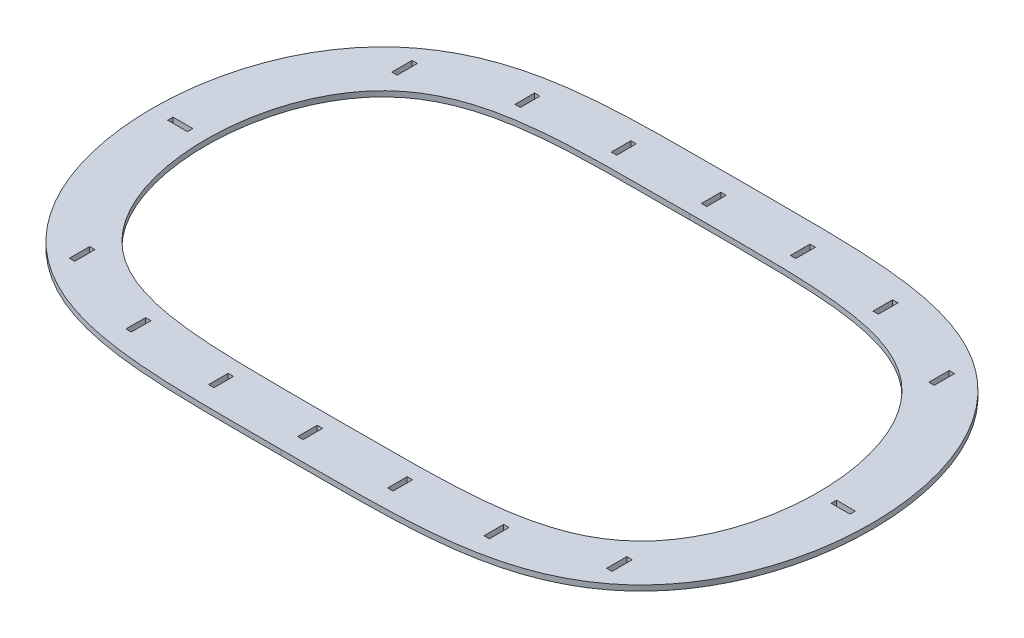
SolidWorks part; units mm, degrees
ref_plane "Front Plane" through (0, 0, 0) normal (0, 0, 1) x (1, 0, 0)
ref_plane "Top Plane" through (0, 0, 0) normal (0, 1, 0) x (1, 0, 0)
ref_plane "Right Plane" through (0, 0, 0) normal (1, 0, 0) x (0, 0, -1)
sketch "Sketch1" plane through (0, 0, 0) normal (0, 1, 0) x (1, 0, 0)
  spline S0 degree 4 poles (0, 129.0994) (4.3298, 129.0999) (12.9895, 129.0995) (25.9763, 129.0992) (43.2902, 129.014) (60.6007, 128.6712) (77.8947, 127.8129) (95.543, 126.046) (113.014, 122.896) (130.0464, 117.7971) (146.1581, 110.2269) (160.4313, 100.265) (172.6933, 87.9119) (182.6634, 73.6634) (190.3404, 58.0791) (195.8654, 41.6227) (199.4008, 24.6362) (201.0699, 7.3707) (200.9352, -9.9735) (198.9912, -27.2107) (195.1663, -44.1354) (189.3287, -60.4854) (181.3147, -75.9018) (170.9944, -89.9023) (157.8662, -102.4377) (141.9679, -112.6829) (124.642, -119.7567) (106.7084, -124.2192) (88.4462, -126.9034) (70.0513, -128.3227) (45.6298, -129.0998) (25.3491, -129.0993) (10.1399, -129.0994) (0, -129.0994) knots 0 0 0 0 0 0.03122 0.06244 0.093642 0.124843 0.156053 0.187263 0.221451 0.252662 0.283872 0.315082 0.346292 0.377502 0.408713 0.439923 0.471133 0.502344 0.533554 0.564765 0.595975 0.627185 0.658396 0.689606 0.720816 0.757371 0.793926 0.823852 0.853778 0.890332 0.926886 1 1 1 1 1 construction
  spline S1 degree 4 poles (0, 129.0994) (4.3298, 129.0999) (12.9895, 129.0995) (25.9763, 129.0992) (43.2902, 129.014) (60.6007, 128.6712) (77.8947, 127.8129) (95.543, 126.046) (113.014, 122.896) (130.0464, 117.7971) (146.1581, 110.2269) (160.4313, 100.265) (172.6933, 87.9119) (182.6634, 73.6634) (190.3404, 58.0791) (195.8654, 41.6227) (199.4008, 24.6362) (201.0699, 7.3707) (200.9352, -9.9735) (198.9912, -27.2107) (195.1663, -44.1354) (189.3287, -60.4854) (181.3147, -75.9018) (170.9944, -89.9023) (157.8662, -102.4377) (141.9679, -112.6829) (124.642, -119.7567) (106.7084, -124.2192) (88.4462, -126.9034) (70.0513, -128.3227) (45.6298, -129.0998) (25.3491, -129.0993) (10.1399, -129.0994) (0, -129.0994) knots 0 0 0 0 0 0.03122 0.06244 0.093642 0.124843 0.156053 0.187263 0.221451 0.252662 0.283872 0.315082 0.346292 0.377502 0.408713 0.439923 0.471133 0.502344 0.533554 0.564765 0.595975 0.627185 0.658396 0.689606 0.720816 0.757371 0.793926 0.823852 0.853778 0.890332 0.926886 1 1 1 1 1
  spline S2 degree 4 poles (0, 129.0994) (-4.3298, 129.0999) (-12.9895, 129.0995) (-25.9763, 129.0992) (-43.2902, 129.014) (-60.6007, 128.6712) (-77.8947, 127.8129) (-95.543, 126.046) (-113.014, 122.896) (-130.0464, 117.7971) (-146.1581, 110.2269) (-160.4313, 100.265) (-172.6933, 87.9119) (-182.6634, 73.6634) (-190.3404, 58.0791) (-195.8654, 41.6227) (-199.4008, 24.6362) (-201.07, 7.3707) (-200.9352, -9.9735) (-198.9912, -27.2107) (-195.1663, -44.1354) (-189.3287, -60.4854) (-181.3147, -75.9018) (-170.9944, -89.9023) (-157.8662, -102.4377) (-141.9679, -112.6829) (-124.642, -119.7567) (-106.7084, -124.2192) (-88.4462, -126.9034) (-70.0513, -128.3227) (-45.6298, -129.0998) (-25.3491, -129.0993) (-10.1399, -129.0994) (0, -129.0994) knots 0 0 0 0 0 0.03122 0.06244 0.093642 0.124843 0.156053 0.187263 0.221451 0.252662 0.283872 0.315082 0.346292 0.377502 0.408713 0.439923 0.471133 0.502344 0.533554 0.564765 0.595975 0.627185 0.658396 0.689606 0.720816 0.757371 0.793926 0.823852 0.853778 0.890332 0.926886 1 1 1 1 1 construction
  spline S3 degree 4 poles (0, 129.0994) (-4.3298, 129.0999) (-12.9895, 129.0995) (-25.9763, 129.0992) (-43.2902, 129.014) (-60.6007, 128.6712) (-77.8947, 127.8129) (-95.543, 126.046) (-113.014, 122.896) (-130.0464, 117.7971) (-146.1581, 110.2269) (-160.4313, 100.265) (-172.6933, 87.9119) (-182.6634, 73.6634) (-190.3404, 58.0791) (-195.8654, 41.6227) (-199.4008, 24.6362) (-201.07, 7.3707) (-200.9352, -9.9735) (-198.9912, -27.2107) (-195.1663, -44.1354) (-189.3287, -60.4854) (-181.3147, -75.9018) (-170.9944, -89.9023) (-157.8662, -102.4377) (-141.9679, -112.6829) (-124.642, -119.7567) (-106.7084, -124.2192) (-88.4462, -126.9034) (-70.0513, -128.3227) (-45.6298, -129.0998) (-25.3491, -129.0993) (-10.1399, -129.0994) (0, -129.0994) knots 0 0 0 0 0 0.03122 0.06244 0.093642 0.124843 0.156053 0.187263 0.221451 0.252662 0.283872 0.315082 0.346292 0.377502 0.408713 0.439923 0.471133 0.502344 0.533554 0.564765 0.595975 0.627185 0.658396 0.689606 0.720816 0.757371 0.793926 0.823852 0.853778 0.890332 0.926886 1 1 1 1 1
extrude "body" add sketch "Sketch1" along normal blind 3 contours S1 S3
sketch "Sketch6" plane through (0, 3, 0) normal (0, 1, 0) x (1, 0, 0)
  spline S5 degree 3 poles (-1285.0609, -2635.3961) (-864.743, -75.7384) (-425.088, -99.3062) (19.1852, -99.0955) (23.9815, -99.0904) (33.5738, -99.0537) (38.3699, -99.0221) (47.9616, -98.8962) (52.7579, -98.802) (62.3467, -98.4962) (67.1336, -98.285) (76.6828, -97.6696) (81.4451, -97.2657) (90.9316, -96.1585) (95.6558, -95.456) (102.6989, -94.0635) (105.0393, -93.5425) (108.5366, -92.6558) (109.7001, -92.3427) (112.0221, -91.6775) (113.1817, -91.3249) (118.9246, -89.468) (123.3747, -87.6745) (129.7643, -84.3748) (131.8465, -83.1733) (134.8899, -81.2003) (135.894, -80.5119) (137.8536, -79.0903) (138.8101, -78.3567) (143.4771, -74.5763) (146.8407, -71.1906) (150.6186, -66.542) (151.3528, -65.5915) (152.7797, -63.6497) (153.4733, -62.657) (155.4863, -59.6292) (156.7253, -57.5647) (160.1696, -51.2497) (162.1054, -46.8788) (164.5604, -40.1222) (165.3033, -37.8364) (166.3108, -34.36) (166.6291, -33.1922) (167.2268, -30.8567) (167.507, -29.6871) (168.8178, -23.8304) (169.5816, -19.117) (170.5999, -9.6403) (170.8539, -4.8769) (170.8586, 2.3051) (170.7971, 4.7053) (170.6075, 8.3151) (170.528, 9.5208) (170.3371, 11.9209) (170.2256, 13.117) (169.5883, 19.0778) (168.8243, 23.784) (166.7551, 33.0633) (165.4507, 37.6366) (163.0193, 44.3799) (162.1291, 46.6081) (160.6593, 49.9173) (160.1456, 51.0173) (159.078, 53.1894) (158.524, 54.2618) (155.6502, 59.5536) (153.0206, 63.5638) (149.2401, 68.2433) (148.4591, 69.1624) (146.8451, 70.9655) (146.0094, 71.852) (143.4475, 74.429) (141.6634, 76.0417) (136.0871, 80.5693) (132.0698, 83.1727) (126.7078, 85.9558) (125.6156, 86.4903) (123.4176, 87.5057) (122.3112, 87.9872) (118.9711, 89.3599) (116.7168, 90.1793) (109.885, 92.3962) (105.2389, 93.5553) (98.1742, 94.9611) (95.8032, 95.3737) (91.0346, 96.1061) (88.6465, 96.4244) (81.481, 97.263) (76.6986, 97.6685) (67.1268, 98.2855) (62.3375, 98.4965) (52.7547, 98.802) (47.9612, 98.8963) (38.372, 99.0221) (33.5762, 99.0536) (23.9839, 99.0903) (19.1872, 99.0954) (-464.0952, 99.336) (-943.5394, 72.5987) (-1333.0254, 2577.4402) knots -2.832138 -2.832138 -2.832138 -2.832138 0.03125 0.03125 0.0625 0.0625 0.09375 0.09375 0.125 0.125 0.15625 0.15625 0.1875 0.1875 0.21875 0.21875 0.234375 0.234375 0.242188 0.242188 0.25 0.25 0.28125 0.28125 0.296875 0.296875 0.304688 0.304688 0.3125 0.3125 0.34375 0.34375 0.351563 0.351563 0.359375 0.359375 0.375 0.375 0.40625 0.40625 0.421875 0.421875 0.429688 0.429688 0.4375 0.4375 0.46875 0.46875 0.5 0.5 0.515625 0.515625 0.523438 0.523438 0.53125 0.53125 0.5625 0.5625 0.59375 0.59375 0.609375 0.609375 0.617188 0.617188 0.625 0.625 0.65625 0.65625 0.664063 0.664063 0.671875 0.671875 0.6875 0.6875 0.71875 0.71875 0.726563 0.726563 0.734375 0.734375 0.75 0.75 0.78125 0.78125 0.796875 0.796875 0.8125 0.8125 0.84375 0.84375 0.875 0.875 0.90625 0.90625 0.9375 0.9375 0.96875 0.96875 4.085999 4.085999 4.085999 4.085999 only from (0, -99.0994) to (0, 99.0994)
  spline S6 degree 3 poles (1397.3598, 2549.0539) (939.196, 72.8031) (462.3033, 99.3351) (-19.1856, 99.0954) (-23.9819, 99.0903) (-33.5745, 99.0536) (-38.3706, 99.0221) (-47.9625, 98.8962) (-52.7589, 98.802) (-62.3478, 98.4961) (-67.1348, 98.285) (-76.6842, 97.6695) (-81.4467, 97.2655) (-90.9333, 96.1583) (-95.6577, 95.4559) (-102.701, 94.0631) (-105.0415, 93.5419) (-108.5389, 92.655) (-109.7024, 92.3419) (-112.0245, 91.6767) (-113.184, 91.3242) (-118.9268, 89.4676) (-123.3764, 87.6734) (-129.7661, 84.374) (-131.8484, 83.1724) (-134.8917, 81.1991) (-135.8958, 80.5106) (-137.8552, 79.089) (-138.8116, 78.3554) (-143.4783, 74.5751) (-146.8418, 71.1894) (-150.6197, 66.5406) (-151.354, 65.59) (-152.7809, 63.6482) (-153.4746, 62.6552) (-155.4873, 59.6275) (-156.7262, 57.5631) (-160.1704, 51.2481) (-162.1061, 46.8771) (-164.561, 40.1203) (-165.3039, 37.8343) (-166.3115, 34.3577) (-166.6296, 33.19) (-167.2273, 30.8546) (-167.5074, 29.685) (-168.8181, 23.8284) (-169.5818, 19.1151) (-170.6, 9.6383) (-170.854, 4.8748) (-170.8586, -2.3075) (-170.797, -4.7078) (-170.6074, -8.3179) (-170.5278, -9.5236) (-170.3369, -11.9235) (-170.2254, -13.1195) (-169.588, -19.0801) (-168.8239, -23.7862) (-166.7545, -33.0656) (-165.4499, -37.6391) (-163.0181, -44.3828) (-162.1279, -46.6111) (-160.6577, -49.9206) (-160.1439, -51.0207) (-159.0763, -53.1926) (-158.5224, -54.2649) (-155.6487, -59.5563) (-153.0188, -63.5663) (-149.2378, -68.246) (-148.4568, -69.1651) (-146.8426, -70.9683) (-146.0067, -71.8547) (-143.4449, -74.4313) (-141.661, -76.0438) (-136.0848, -80.5711) (-132.067, -83.1741) (-126.7046, -85.9575) (-125.6124, -86.4921) (-123.4146, -87.5073) (-122.3081, -87.9887) (-118.9681, -89.3609) (-116.7139, -90.18) (-109.8822, -92.3972) (-105.2359, -93.5559) (-98.1709, -94.9615) (-95.7998, -95.3742) (-91.0309, -96.1066) (-88.6431, -96.4249) (-81.478, -97.2633) (-76.6958, -97.6687) (-67.1244, -98.2856) (-62.3352, -98.4966) (-52.7528, -98.8021) (-47.9595, -98.8963) (-38.3706, -99.0221) (-33.5751, -99.0537) (-23.983, -99.0904) (-19.1865, -99.0955) (426.659, -99.307) (868.5614, -75.5661) (1217.4028, -2663.1697) knots -3.074556 -3.074556 -3.074556 -3.074556 0.03125 0.03125 0.0625 0.0625 0.09375 0.09375 0.125 0.125 0.15625 0.15625 0.1875 0.1875 0.21875 0.21875 0.234375 0.234375 0.242187 0.242187 0.25 0.25 0.28125 0.28125 0.296875 0.296875 0.304687 0.304687 0.3125 0.3125 0.34375 0.34375 0.351562 0.351562 0.359375 0.359375 0.375 0.375 0.40625 0.40625 0.421875 0.421875 0.429687 0.429687 0.4375 0.4375 0.46875 0.46875 0.5 0.5 0.515625 0.515625 0.523437 0.523437 0.53125 0.53125 0.5625 0.5625 0.59375 0.59375 0.609375 0.609375 0.617187 0.617187 0.625 0.625 0.65625 0.65625 0.664062 0.664062 0.671875 0.671875 0.6875 0.6875 0.71875 0.71875 0.726562 0.726562 0.734375 0.734375 0.75 0.75 0.78125 0.78125 0.796875 0.796875 0.8125 0.8125 0.84375 0.84375 0.875 0.875 0.90625 0.90625 0.9375 0.9375 0.96875 0.96875 3.842203 3.842203 3.842203 3.842203 only from (0, 99.0994) to (0, -99.0994)
  spline S7 degree 3 poles (0, -99.0994) (4.7963, -99.0994) (9.5926, -99.1) (19.1852, -99.0955) (23.9815, -99.0904) (33.5738, -99.0537) (38.3699, -99.0221) (47.9616, -98.8962) (52.7579, -98.802) (62.3467, -98.4962) (67.1336, -98.285) (76.6828, -97.6696) (81.4451, -97.2657) (90.9316, -96.1585) (95.6558, -95.456) (102.6989, -94.0635) (105.0393, -93.5425) (108.5366, -92.6558) (109.7001, -92.3427) (112.0221, -91.6775) (113.1817, -91.3249) (118.9246, -89.468) (123.3747, -87.6745) (129.7643, -84.3748) (131.8465, -83.1733) (134.8899, -81.2003) (135.894, -80.5119) (137.8536, -79.0903) (138.8101, -78.3567) (143.4771, -74.5763) (146.8407, -71.1906) (150.6186, -66.542) (151.3528, -65.5915) (152.7797, -63.6497) (153.4733, -62.657) (155.4863, -59.6292) (156.7253, -57.5647) (160.1696, -51.2497) (162.1054, -46.8788) (164.5604, -40.1222) (165.3033, -37.8364) (166.3108, -34.36) (166.6291, -33.1922) (167.2268, -30.8567) (167.507, -29.6871) (168.8178, -23.8304) (169.5816, -19.117) (170.5999, -9.6403) (170.8539, -4.8769) (170.8586, 2.3051) (170.7971, 4.7053) (170.6075, 8.3151) (170.528, 9.5208) (170.3371, 11.9209) (170.2256, 13.117) (169.5883, 19.0778) (168.8243, 23.784) (166.7551, 33.0633) (165.4507, 37.6366) (163.0193, 44.3799) (162.1291, 46.6081) (160.6593, 49.9173) (160.1456, 51.0173) (159.078, 53.1894) (158.524, 54.2618) (155.6502, 59.5536) (153.0206, 63.5638) (149.2401, 68.2433) (148.4591, 69.1624) (146.8451, 70.9655) (146.0094, 71.852) (143.4475, 74.429) (141.6634, 76.0417) (136.0871, 80.5693) (132.0698, 83.1727) (126.7078, 85.9558) (125.6156, 86.4903) (123.4176, 87.5057) (122.3112, 87.9872) (118.9711, 89.3599) (116.7168, 90.1793) (109.885, 92.3962) (105.2389, 93.5553) (98.1742, 94.9611) (95.8032, 95.3737) (91.0346, 96.1061) (88.6465, 96.4244) (81.481, 97.263) (76.6986, 97.6685) (67.1268, 98.2855) (62.3375, 98.4965) (52.7547, 98.802) (47.9612, 98.8963) (38.372, 99.0221) (33.5762, 99.0536) (23.9839, 99.0903) (19.1872, 99.0954) (9.5937, 99.1002) (4.7969, 99.0999) (0, 99.0994) knots 0 0 0 0 0.03125 0.03125 0.0625 0.0625 0.09375 0.09375 0.125 0.125 0.15625 0.15625 0.1875 0.1875 0.21875 0.21875 0.234375 0.234375 0.242188 0.242188 0.25 0.25 0.28125 0.28125 0.296875 0.296875 0.304688 0.304688 0.3125 0.3125 0.34375 0.34375 0.351563 0.351563 0.359375 0.359375 0.375 0.375 0.40625 0.40625 0.421875 0.421875 0.429688 0.429688 0.4375 0.4375 0.46875 0.46875 0.5 0.5 0.515625 0.515625 0.523438 0.523438 0.53125 0.53125 0.5625 0.5625 0.59375 0.59375 0.609375 0.609375 0.617188 0.617188 0.625 0.625 0.65625 0.65625 0.664063 0.664063 0.671875 0.671875 0.6875 0.6875 0.71875 0.71875 0.726563 0.726563 0.734375 0.734375 0.75 0.75 0.78125 0.78125 0.796875 0.796875 0.8125 0.8125 0.84375 0.84375 0.875 0.875 0.90625 0.90625 0.9375 0.9375 0.96875 0.96875 1 1 1 1
  spline S8 degree 3 poles (0, 99.0994) (-4.7964, 99.0999) (-9.5928, 99.1002) (-19.1856, 99.0954) (-23.9819, 99.0903) (-33.5745, 99.0536) (-38.3706, 99.0221) (-47.9625, 98.8962) (-52.7589, 98.802) (-62.3478, 98.4961) (-67.1348, 98.285) (-76.6842, 97.6695) (-81.4467, 97.2655) (-90.9333, 96.1583) (-95.6577, 95.4559) (-102.701, 94.0631) (-105.0415, 93.5419) (-108.5389, 92.655) (-109.7024, 92.3419) (-112.0245, 91.6767) (-113.184, 91.3242) (-118.9268, 89.4676) (-123.3764, 87.6734) (-129.7661, 84.374) (-131.8484, 83.1724) (-134.8917, 81.1991) (-135.8958, 80.5106) (-137.8552, 79.089) (-138.8116, 78.3554) (-143.4783, 74.5751) (-146.8418, 71.1894) (-150.6197, 66.5406) (-151.354, 65.59) (-152.7809, 63.6482) (-153.4746, 62.6552) (-155.4873, 59.6275) (-156.7262, 57.5631) (-160.1704, 51.2481) (-162.1061, 46.8771) (-164.561, 40.1203) (-165.3039, 37.8343) (-166.3115, 34.3577) (-166.6296, 33.19) (-167.2273, 30.8546) (-167.5074, 29.685) (-168.8181, 23.8284) (-169.5818, 19.1151) (-170.6, 9.6383) (-170.854, 4.8748) (-170.8586, -2.3075) (-170.797, -4.7078) (-170.6074, -8.3179) (-170.5278, -9.5236) (-170.3369, -11.9235) (-170.2254, -13.1195) (-169.588, -19.0801) (-168.8239, -23.7862) (-166.7545, -33.0656) (-165.4499, -37.6391) (-163.0181, -44.3828) (-162.1279, -46.6111) (-160.6577, -49.9206) (-160.1439, -51.0207) (-159.0763, -53.1926) (-158.5224, -54.2649) (-155.6487, -59.5563) (-153.0188, -63.5663) (-149.2378, -68.246) (-148.4568, -69.1651) (-146.8426, -70.9683) (-146.0067, -71.8547) (-143.4449, -74.4313) (-141.661, -76.0438) (-136.0848, -80.5711) (-132.067, -83.1741) (-126.7046, -85.9575) (-125.6124, -86.4921) (-123.4146, -87.5073) (-122.3081, -87.9887) (-118.9681, -89.3609) (-116.7139, -90.18) (-109.8822, -92.3972) (-105.2359, -93.5559) (-98.1709, -94.9615) (-95.7998, -95.3742) (-91.0309, -96.1066) (-88.6431, -96.4249) (-81.478, -97.2633) (-76.6958, -97.6687) (-67.1244, -98.2856) (-62.3352, -98.4966) (-52.7528, -98.8021) (-47.9595, -98.8963) (-38.3706, -99.0221) (-33.5751, -99.0537) (-23.983, -99.0904) (-19.1865, -99.0955) (-9.5934, -99.1) (-4.7967, -99.0994) (0, -99.0994) knots 0 0 0 0 0.03125 0.03125 0.0625 0.0625 0.09375 0.09375 0.125 0.125 0.15625 0.15625 0.1875 0.1875 0.21875 0.21875 0.234375 0.234375 0.242187 0.242187 0.25 0.25 0.28125 0.28125 0.296875 0.296875 0.304687 0.304687 0.3125 0.3125 0.34375 0.34375 0.351562 0.351562 0.359375 0.359375 0.375 0.375 0.40625 0.40625 0.421875 0.421875 0.429687 0.429687 0.4375 0.4375 0.46875 0.46875 0.5 0.5 0.515625 0.515625 0.523437 0.523437 0.53125 0.53125 0.5625 0.5625 0.59375 0.59375 0.609375 0.609375 0.617187 0.617187 0.625 0.625 0.65625 0.65625 0.664062 0.664062 0.671875 0.671875 0.6875 0.6875 0.71875 0.71875 0.726562 0.726562 0.734375 0.734375 0.75 0.75 0.78125 0.78125 0.796875 0.796875 0.8125 0.8125 0.84375 0.84375 0.875 0.875 0.90625 0.90625 0.9375 0.9375 0.96875 0.96875 1 1 1 1
  dimension "D1" = 30
extrude "cut-inside" cut sketch "Sketch6" against normal blind 50
sketch "Sketch7" plane through (0, 3, 0) normal (0, 1, 0) x (1, 0, 0)
  line L1 (-151.5, 95.6876) -> (-148.5, 95.6876)
  line L2 (-151.5, 95.6876) -> (-151.5, 84.3621)
  line L3 (-151.5, 84.3621) -> (-148.5, 84.3621)
  line L4 (-148.5, 95.6876) -> (-148.5, 84.3621)
  line L5 (-101.5, 114.1082) -> (-98.5, 114.1082)
  line L6 (-101.5, 114.1082) -> (-101.5, 103.1387)
  line L7 (-101.5, 103.1387) -> (-98.5, 103.1387)
  line L8 (-98.5, 114.1082) -> (-98.5, 103.1387)
  line L9 (-51.5, 117.9381) -> (-48.5, 117.9381)
  line L10 (-51.5, 117.9381) -> (-51.5, 107.0244)
  line L11 (-51.5, 107.0244) -> (-48.5, 107.0244)
  line L12 (-48.5, 117.9381) -> (-48.5, 107.0244)
  line L13 (-1.5, 118.1892) -> (1.5, 118.1892)
  line L14 (-1.5, 118.1892) -> (-1.5, 107.2791)
  line L15 (-1.5, 107.2791) -> (1.5, 107.2791)
  line L16 (1.5, 118.1892) -> (1.5, 107.2791)
  line L17 (48.5, 117.9381) -> (51.5, 117.9381)
  line L18 (48.5, 117.9381) -> (48.5, 107.0244)
  line L19 (48.5, 107.0244) -> (51.5, 107.0244)
  line L20 (51.5, 117.9381) -> (51.5, 107.0244)
  line L21 (98.5, 114.1082) -> (101.5, 114.1082)
  line L22 (98.5, 114.1082) -> (98.5, 103.1387)
  line L23 (98.5, 103.1387) -> (101.5, 103.1387)
  line L24 (101.5, 114.1082) -> (101.5, 103.1387)
  line L25 (148.5, 95.6876) -> (151.5, 95.6876)
  line L26 (148.5, 95.6876) -> (148.5, 84.3621)
  line L27 (148.5, 84.3621) -> (151.5, 84.3621)
  line L28 (151.5, 95.6876) -> (151.5, 84.3621)
  line L29 (179.7305, 1.5) -> (190.2938, 1.5)
  line L30 (179.7305, 1.5) -> (179.7305, -1.5)
  line L31 (179.7305, -1.5) -> (190.2938, -1.5)
  line L32 (190.2938, 1.5) -> (190.2938, -1.5)
  line L33 (148.5, -84.3621) -> (151.5, -84.3621)
  line L34 (148.5, -84.3621) -> (148.5, -95.6876)
  line L35 (148.5, -95.6876) -> (151.5, -95.6876)
  line L36 (151.5, -84.3621) -> (151.5, -95.6876)
  line L37 (98.5, -103.1387) -> (101.5, -103.1387)
  line L38 (98.5, -103.1387) -> (98.5, -114.1082)
  line L39 (98.5, -114.1082) -> (101.5, -114.1082)
  line L40 (101.5, -103.1387) -> (101.5, -114.1082)
  line L41 (48.5, -107.0244) -> (51.5, -107.0244)
  line L42 (48.5, -107.0244) -> (48.5, -117.9381)
  line L43 (48.5, -117.9381) -> (51.5, -117.9381)
  line L44 (51.5, -107.0244) -> (51.5, -117.9381)
  line L45 (-1.5, -107.2791) -> (1.5, -107.2791)
  line L46 (-1.5, -107.2791) -> (-1.5, -118.1892)
  line L47 (-1.5, -118.1892) -> (1.5, -118.1892)
  line L48 (1.5, -107.2791) -> (1.5, -118.1892)
  line L49 (-51.5, -107.0244) -> (-48.5, -107.0244)
  line L50 (-51.5, -107.0244) -> (-51.5, -117.9381)
  line L51 (-51.5, -117.9381) -> (-48.5, -117.9381)
  line L52 (-48.5, -107.0244) -> (-48.5, -117.9381)
  line L53 (-101.5, -103.1387) -> (-98.5, -103.1387)
  line L54 (-101.5, -103.1387) -> (-101.5, -114.1082)
  line L55 (-101.5, -114.1082) -> (-98.5, -114.1082)
  line L56 (-98.5, -103.1387) -> (-98.5, -114.1082)
  line L57 (-151.5, -84.3621) -> (-148.5, -84.3621)
  line L58 (-151.5, -84.3621) -> (-151.5, -95.6876)
  line L59 (-151.5, -95.6876) -> (-148.5, -95.6876)
  line L60 (-148.5, -84.3621) -> (-148.5, -95.6876)
  line L61 (-190.8571, 1.5) -> (-179.7305, 1.5)
  line L62 (-190.8571, 1.5) -> (-190.8571, -1.5)
  line L63 (-190.8571, -1.5) -> (-179.7305, -1.5)
  line L64 (-179.7305, 1.5) -> (-179.7305, -1.5)
extrude "Cut-Extrude1" cut sketch "Sketch7" against normal through all
